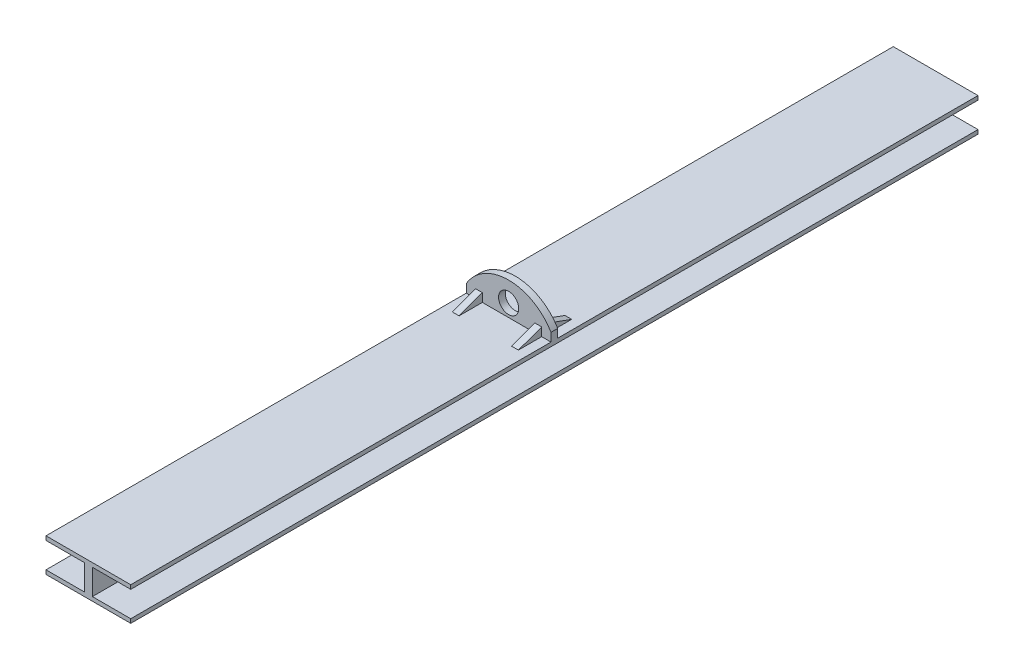
SolidWorks part; units mm, degrees
ref_plane "Alzado" through (0, 0, 0) normal (0, 0, 1) x (1, 0, 0)
ref_plane "Planta" through (0, 0, 0) normal (0, 1, 0) x (1, 0, 0)
ref_plane "Vista lateral" through (0, 0, 0) normal (1, 0, 0) x (0, 0, -1)
sketch "Croquis1" plane through (0, 0, 0) normal (0, 0, 1) x (1, 0, 0)
  line L0 (0, 19.7625) -> (-50, 19.7625)
  line L1 (0, 19.7625) -> (0, -19.7625)
  line L2 (0, -19.7625) -> (-50, -19.7625)
  line L3 (-4.7625, -15) -> (-50, -15)
  line L4 (-4.7625, 15) -> (-4.7625, -15)
  line L5 (-4.7625, 15) -> (-50, 15)
  line L6 (-50, -19.7625) -> (-50, -15)
  line L7 (-50, 19.7625) -> (-50, 15)
  line L8 (10.168, 0) -> (-43.4141, 0) construction
  line L9 (4.7625, 15) -> (4.7625, -15)
  line L10 (4.7625, 15) -> (50, 15)
  line L11 (50, 19.7625) -> (50, 15)
  line L12 (0, 19.7625) -> (50, 19.7625)
  line L13 (0, -19.7625) -> (50, -19.7625)
  line L14 (50, -19.7625) -> (50, -15)
  line L15 (4.7625, -15) -> (50, -15)
  line L16 (0, 19.7625) -> (0, -19.7625)
  line L17 (50, -19.7625) -> (50, -15)
  line L18 (4.7625, -15) -> (4.7625, 15)
  line L19 (50, 15) -> (50, 19.7625)
  dimension "D2" = 50
  dimension "D3" = 15
  dimension "D1" = 4.7625
extrude "Saliente-Extruir1" add sketch "Croquis1" along normal mid plane 1000 contours L8 L9 L10 L11 L12 L1 | L18 L8 L16 L13 L14 L15 | L8 L1 L0 L7 L5 L4 | L16 L8 L4 L3 L6 L2 region at (-19.7803, 15.101, 0) region at (19.7803, 15.101, 0) region at (19.7803, -15.101, 0) region at (-19.7803, -15.101, 0)
sketch "Croquis3" plane through (0, 0, 0) normal (0, 0, 1) x (1, 0, 0)
  line L0 (50, -19.7625) -> (50, -15) construction
  line L1 (4.7625, -15) -> (50, -15) construction
  line L2 (-50, -19.7625) -> (50, -19.7625) construction
  line L3 (-50, -19.7625) -> (-50, -15) construction
  line L4 (-4.7625, -15) -> (-50, -15) construction
  line L5 (50, 19.7625) -> (50, 15) construction
  line L6 (4.7625, 15) -> (50, 15) construction
  line L7 (4.7625, 15) -> (4.7625, -15) construction
  line L8 (-4.7625, 15) -> (-4.7625, -15) construction
  line L9 (-50, 19.7625) -> (-50, 15) construction
  line L10 (-50, 19.7625) -> (50, 19.7625) construction
  line L11 (-4.7625, 15) -> (-50, 15) construction
  line L12 (50, -19.7625) -> (50, -15)
  line L13 (4.7625, -15) -> (50, -15)
  line L14 (-50, -19.7625) -> (50, -19.7625)
  line L15 (-50, -19.7625) -> (-50, -15)
  line L16 (-4.7625, -15) -> (-50, -15)
  line L17 (50, 19.7625) -> (50, 15)
  line L18 (4.7625, 15) -> (50, 15)
  line L19 (4.7625, 15) -> (4.7625, -15)
  line L20 (-4.7625, 15) -> (-4.7625, -15)
  line L21 (-50, 19.7625) -> (-50, 15)
  line L22 (-50, 19.7625) -> (50, 19.7625)
  line L23 (-4.7625, 15) -> (-50, 15)
  line L25 (-50, 19.7625) -> (50, 19.7625)
  line L26 (-50, 19.7625) -> (-50, 29.7625)
  line L27 (-50, 29.7625) -> (50, 29.7625)
  line L28 (50, 19.7625) -> (50, 29.7625)
  arc A0 (-50, 29.7625) -> (50, 29.7625) centre (0, 0) cw
  point P9 (0, 0)
  dimension "D1" = 10
extrude "Saliente-Extruir2" add sketch "Croquis3" along normal mid plane 7.9375 contours A0 L27 | L22 L28 L27 L26 region at (0, 24.7625, 0) region at (0, 41.4103, 0)
sketch "Croquis4" plane through (0, 0, 3.9688) normal (0, 0, 1) x (1, 0, 0)
  line L0 (-50, 19.7625) -> (50, 19.7625) construction
  line L1 (0, -7.4326) -> (0, 62.6638) construction
  circle A0 centre (0, 34.7625) radius 11.9063
  dimension "D1" = 23.8125
  dimension "D2" = 15
extrude "Cortar-Extruir1" cut sketch "Croquis4" against normal blind 7.9375
ref_plane "Plano1" through (35, 0, 0) normal (1, 0, 0) x (0, 0, -1)
ref_plane "Plano2" through (-35, 0, 0) normal (1, 0, 0) x (0, 0, -1)
sketch "Croquis6" plane through (35, 0, 0) normal (1, 0, 0) x (0, 0, -1)
  line L0 (0, 89.1427) -> (0, -55.5294) construction
  line L1 (-3.9688, 29.7625) -> (-31.4435, 19.7625)
  line L2 (-500, 19.7625) -> (-3.9688, 19.7625) construction
  dimension "D1" = 20
rib "Nervio6" sketch "Croquis6" sketch "Croquis6" thickness 7.9375 extrusion direction parallel to sketch draft on no parameters "D1"=7.9375
mirror "Simetría1" about plane through (0, 0, 0) normal (0, 0, 1) of "Nervio6"
mirror "Simetría2" about plane through (0, 0, 0) normal (1, 0, 0) of "Nervio6", "Simetría1"
